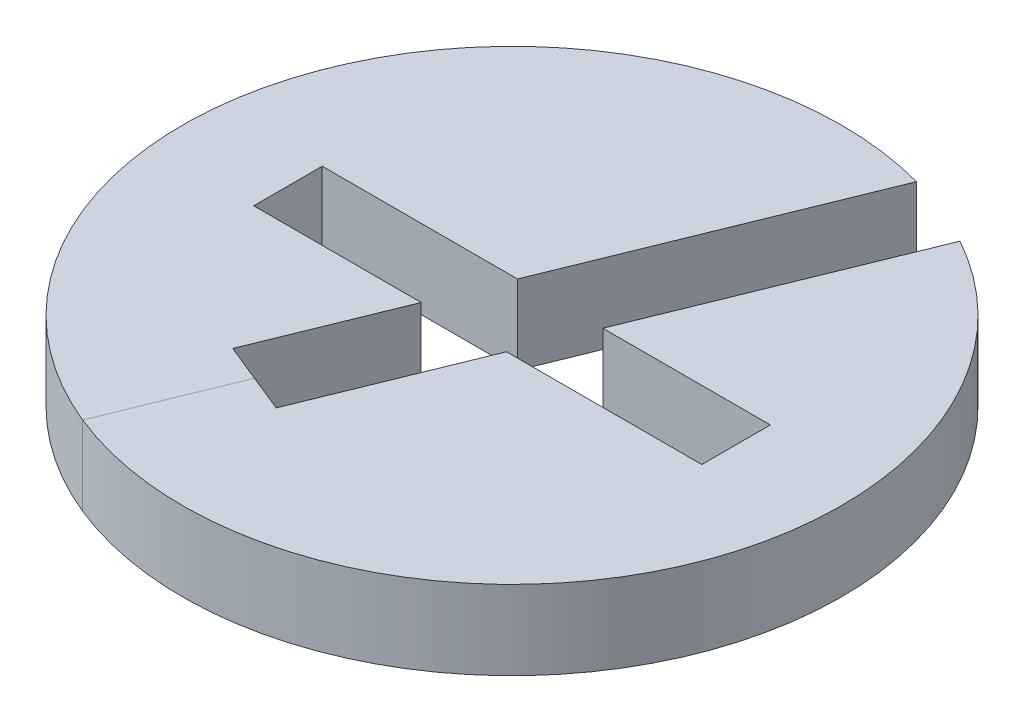
SolidWorks part; units mm, degrees
ref_plane "Front Plane" through (0, 0, 0) normal (0, 0, 1) x (1, 0, 0)
ref_plane "Top Plane" through (0, 0, 0) normal (0, 1, 0) x (1, 0, 0)
ref_plane "Right Plane" through (0, 0, 0) normal (1, 0, 0) x (0, 0, -1)
sketch "Sketch1" plane through (0, 0, 0) normal (0, 1, 0) x (1, 0, 0)
  line L0 (-12.5, 0) -> (12.5, 0) construction
  line L1 (-12.5, 0) -> (12.5, 0) construction
  circle A0 centre (0, 0) radius 12.5
extrude "Boss-Extrude1" add sketch "Sketch1" along normal blind 1.5 and the other way blind 1.5
sketch "Sketch2" plane through (0, -1.5, 0) normal (0, -1, 0) x (1, 0, 0)
  line L1 (-8.5, -1.3) -> (8.5, -1.3)
  line L2 (-8.5, -1.3) -> (-8.5, 1.3)
  line L3 (-8.5, 1.3) -> (8.5, 1.3)
  line L4 (8.5, -1.3) -> (8.5, 1.3)
  line L5 (0, 1.3) -> (0, -1.3) construction
  line L6 (-8.5, 0) -> (8.5, 0) construction
  point P0 (0, 0)
  dimension "D1" = 2.6
extrude "Cut-Extrude1" cut sketch "Sketch2" against normal through all
sketch "Sketch3" plane through (0, 0, 0) normal (0, -1, 0) x (1, 0, 0)
  line L0 (3.313, -12.1459) -> (-4.2115, 6.3846)
  line L1 (3.313, -12.1459) -> (6.0926, -11.0173)
  line L2 (-4.2115, 6.3846) -> (-1.4319, 7.5133)
  line L3 (6.0926, -11.0173) -> (-1.4319, 7.5133)
  line L4 (-2.8217, 6.949) -> (4.7028, -11.5816) construction
  line L5 (-0.4492, -2.8807) -> (2.3304, -1.752) construction
  line L6 (0, -1000) -> (0, 49000) construction
  circle A0 centre (0, 0) radius 12.5 construction
  point P0 (-4.7028, 11.5816)
  point P1 (0.9406, -2.3163)
  dimension "D1" = 3
  dimension "D2" = 22.1
  dimension "D3" = 5
extrude "Cut-Extrude2" cut sketch "Sketch3" against normal through all both and the other way through all
ref_axis "Axis1" through (-2.8217, 0, 6.949) along (0.3762, 0, -0.9265)
ref_plane "Plane1" through (0, 0, 0) normal (-0.9265, 0, -0.3762) x (-0.3762, 0, 0.9265)
split "Split2" trim tools "Plane1" bodies to split 103 resulting bodies 110 111
